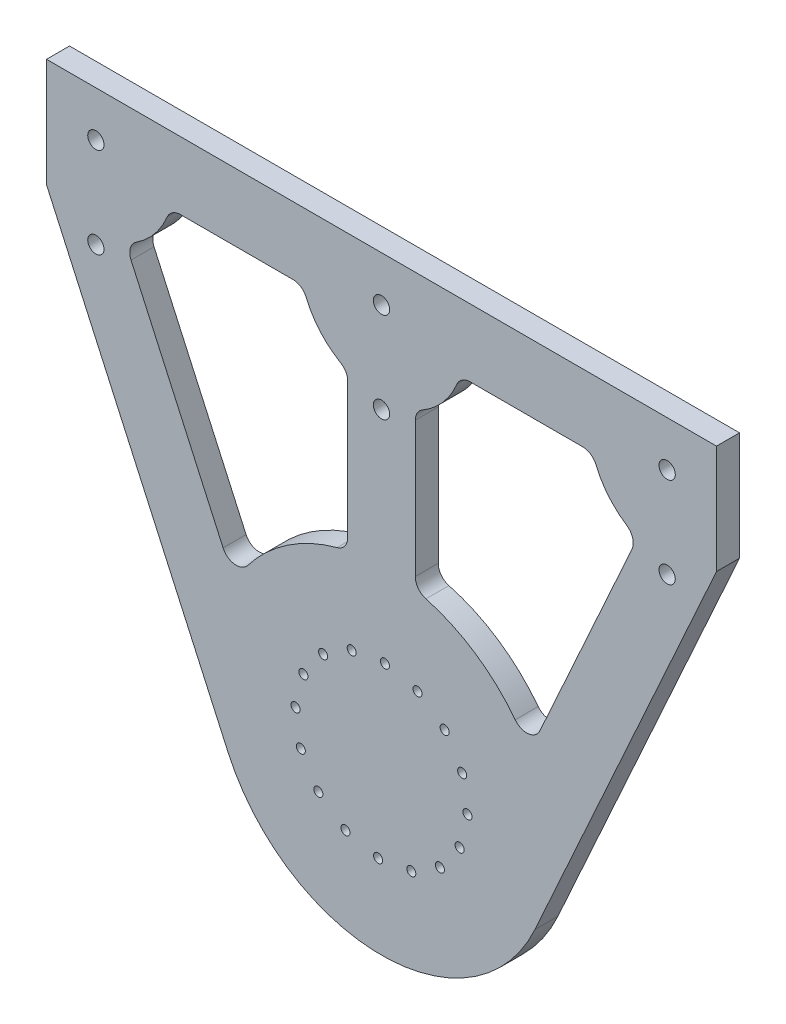
SolidWorks part; units mm, degrees
ref_plane "Front Plane" through (0, 0, 0) normal (0, 0, 1) x (1, 0, 0)
ref_plane "Top Plane" through (0, 0, 0) normal (0, 1, 0) x (1, 0, 0)
ref_plane "Right Plane" through (0, 0, 0) normal (1, 0, 0) x (0, 0, -1)
sketch "Sketch1" plane through (0, 0, 0) normal (0, 0, 1) x (1, 0, 0)
  line L1 (92.5, 121.5) -> (-92.5, 121.5)
  line L3 (0, 0) -> (0, 121.5) construction
  line L4 (-92.5, 121.5) -> (-92.5, 91.5)
  line L5 (-92.5, 91.5) -> (-42.3564, -19.1882)
  line L6 (92.5, 121.5) -> (92.5, 91.5)
  line L7 (92.5, 91.5) -> (42.3564, -19.1882)
  line L8 (42.3564, -19.1882) -> (-42.3564, -19.1882) construction
  circle A0 centre (0, 0) radius 46.5 construction
  arc A1 (-42.3564, -19.1882) -> (42.3564, -19.1882) centre (0, 0) ccw
  dimension "D1" = 93
  dimension "D2" = 185
  dimension "D3" = 121.5
  dimension "D4" = 30
extrude "Boss-Extrude1" add sketch "Sketch1" along normal mid plane 6.35
sketch "Sketch3" plane through (0, 0, -3.175) normal (0, 0, -1) x (-1, 0, 0)
  circle A0 centre (17.4402, -16.1215) radius 1.25 construction
  circle A1 centre (22.282, -8.2203) radius 1.25 construction
  circle A2 centre (9.9432, -21.5684) radius 1.25 construction
  circle A3 centre (0.9324, -23.7317) radius 1.25 construction
  circle A4 centre (-8.2203, -22.282) radius 1.25 construction
  circle A5 centre (-16.1215, -17.4402) radius 1.25 construction
  circle A6 centre (-21.5684, -9.9432) radius 1.25 construction
  circle A7 centre (-23.7317, -0.9324) radius 1.25 construction
  circle A8 centre (-22.282, 8.2203) radius 1.25 construction
  circle A9 centre (-17.4402, 16.1215) radius 1.25 construction
  circle A10 centre (-9.9432, 21.5684) radius 1.25 construction
  circle A11 centre (-0.9324, 23.7317) radius 1.25 construction
  circle A12 centre (8.2203, 22.282) radius 1.25 construction
  circle A13 centre (16.1215, 17.4402) radius 1.25 construction
  circle A14 centre (21.5684, 9.9432) radius 1.25 construction
  circle A15 centre (23.7317, 0.9324) radius 1.25 construction
  circle A16 centre (17.4402, -16.1215) radius 1.25
  circle A17 centre (22.282, -8.2203) radius 1.25
  circle A18 centre (9.9432, -21.5684) radius 1.25
  circle A19 centre (0.9324, -23.7317) radius 1.25
  circle A20 centre (-8.2203, -22.282) radius 1.25
  circle A21 centre (-16.1215, -17.4402) radius 1.25
  circle A22 centre (-21.5684, -9.9432) radius 1.25
  circle A23 centre (-23.7317, -0.9324) radius 1.25
  circle A24 centre (-22.282, 8.2203) radius 1.25
  circle A25 centre (-17.4402, 16.1215) radius 1.25
  circle A26 centre (-9.9432, 21.5684) radius 1.25
  circle A27 centre (-0.9324, 23.7317) radius 1.25
  circle A28 centre (8.2203, 22.282) radius 1.25
  circle A29 centre (16.1215, 17.4402) radius 1.25
  circle A30 centre (21.5684, 9.9432) radius 1.25
  circle A31 centre (23.7317, 0.9324) radius 1.25
extrude "Cut-Extrude2" cut sketch "Sketch3" against normal through all both and the other way through all
ref_plane "Plane1" through (0, 91.5, 0) normal (0, 1, 0) x (1, 0, 0)
ref_plane "Plane2" through (0, 106.5, 0) normal (0, 1, 0) x (1, 0, 0)
sketch "Sketch6" plane through (0, 0, -3.175) normal (0, 0, -1) x (-1, 0, 0)
  line L0 (0, 0) -> (0, 121.5) construction
  line L1 (-92.5, 121.5) -> (-77.5, 121.5) construction
  line L2 (-92.5, 121.5) -> (-92.5, 91.5) construction
  line L3 (-92.5, 91.5) -> (-77.5, 91.5) construction
  line L4 (-77.5, 121.5) -> (-77.5, 91.5) construction
  line L5 (-92.5, 121.5) -> (92.5, 121.5) construction
  line L6 (-85, 121.5) -> (-85, 106.5) construction
  line L11 (-77.5, 106.5) -> (-92.5, 106.5) construction
  line L12 (-7.5, 121.5) -> (7.5, 121.5) construction
  line L13 (-7.5, 121.5) -> (-7.5, 91.5) construction
  line L14 (-7.5, 91.5) -> (7.5, 91.5) construction
  line L15 (7.5, 121.5) -> (7.5, 91.5) construction
  line L16 (-85, 91.5) -> (-85, 106.5) construction
  circle A0 centre (-85, 114) radius 2.25
  circle A1 centre (-85, 99) radius 2.25
  circle A2 centre (0, 114) radius 2.25
  circle A3 centre (0, 99) radius 2.25
  circle A6 centre (85, 114) radius 2.25
  circle A7 centre (85, 99) radius 2.25
  point P18 (0, 121.5)
  point P35 (-85, 114)
  point P38 (-85, 99)
  dimension "D3" = 4.5
  dimension "D1" = 30
  dimension "D2" = 15
sketch "Sketch12" plane through (0, 0, -3.175) normal (0, 0, -1) x (-1, 0, 0)
  line L0 (0, -46.5) -> (0, 121.5) construction
  line L1 (-92.5, 121.5) -> (92.5, 121.5) construction
  line L2 (-87, 116) -> (-92.5, 116) construction
  line L3 (-87, 116) -> (-73, 116) construction
  line L4 (-87, 116) -> (-87, 102) construction
  line L5 (-87, 102) -> (-73, 102) construction
  line L6 (-73, 116) -> (-73, 102) construction
  line L7 (-92.5, 91.5) -> (-92.5, 121.5) construction
  line L8 (-87, 116) -> (-87, 121.5) construction
  line L9 (12.5, 121.5) -> (-12.5, 121.5) construction
  line L11 (-7, 102) -> (7, 102) construction
  line L12 (-7, 102) -> (-7, 116) construction
  line L13 (-7, 116) -> (7, 116) construction
  line L14 (7, 102) -> (7, 116) construction
  circle A0 centre (-7, 102) radius 2.25
  circle A2 centre (7, 102) radius 2.25
  circle A4 centre (7, 116) radius 2.25
  circle A5 centre (-87, 116) radius 2.25
  circle A6 centre (-73, 116) radius 2.25
  circle A7 centre (-73, 102) radius 2.25
  circle A8 centre (-87, 102) radius 2.25
  arc A9 (-42.3564, -19.1882) -> (42.3564, -19.1882) centre (0, 0) ccw construction
  circle A10 centre (87, 102) radius 2.25
  circle A11 centre (73, 102) radius 2.25
  circle A12 centre (73, 116) radius 2.25
  circle A13 centre (87, 116) radius 2.25
  circle A14 centre (-7, 116) radius 2.25
  point P22 (-87, 109)
  point P23 (-7, 109)
  point P24 (0, 116)
  dimension "D3" = 4.5
  dimension "D1" = 5.5
  dimension "D2" = 14
extrude "Cut-Extrude6" cut sketch "Sketch12" against normal through all both and the other way through all
sketch "Sketch13" plane through (0, 0, -3.175) normal (0, 0, -1) x (-1, 0, 0)
  line L0 (-40.7392, 22.418) -> (-70.6842, 88.5191)
  line L1 (40.7392, 22.418) -> (70.6842, 88.5191)
  line L2 (-9.3209, 88.5215) -> (-9.3209, 45.5562)
  line L3 (9.3209, 88.5215) -> (9.3209, 45.5562)
  line L7 (-7, 102) -> (7, 116) construction
  line L8 (-87, 102) -> (-73, 116) construction
  line L9 (58.3545, 102.8582) -> (21.6455, 102.8582)
  line L10 (-58.3545, 102.8582) -> (-21.6455, 102.8582)
  line L11 (25.3758, -11.4957) -> (73.8582, 95.5256)
  line L12 (73.8582, 95.5256) -> (73.8582, 102.8582)
  line L13 (73.8582, 102.8582) -> (-73.8582, 102.8582)
  line L14 (-73.8582, 102.8582) -> (-73.8582, 95.5256)
  line L15 (-73.8582, 95.5256) -> (-25.3758, -11.4957)
  line L16 (25.3758, -11.4957) -> (73.8582, 95.5256) construction
  line L17 (73.8582, 95.5256) -> (73.8582, 102.8582) construction
  line L18 (73.8582, 102.8582) -> (-73.8582, 102.8582) construction
  line L19 (-73.8582, 102.8582) -> (-73.8582, 95.5256) construction
  line L20 (-73.8582, 95.5256) -> (-25.3758, -11.4957) construction
  line L23 (0, 0) -> (0, 109) construction
  arc A0 (-40.7392, 22.418) -> (40.7392, 22.418) centre (0, 0) cw construction
  circle A1 centre (0, 0) radius 27.8582 construction
  arc A2 (-25.3758, -11.4957) -> (25.3758, -11.4957) centre (0, 0) ccw
  arc A3 (-25.3758, -11.4957) -> (25.3758, -11.4957) centre (0, 0) ccw construction
  circle A4 centre (7, 116) radius 2.25 construction
  circle A5 centre (-7, 102) radius 2.25 construction
  circle A6 centre (-73, 116) radius 2.25 construction
  circle A7 centre (-87, 102) radius 2.25 construction
  circle A8 centre (7, 116) radius 2.25 construction
  circle A9 centre (-7, 102) radius 2.25 construction
  circle A10 centre (-73, 116) radius 2.25 construction
  circle A11 centre (-87, 102) radius 2.25 construction
  circle A12 centre (-80, 109) radius 22.5 construction
  circle A13 centre (0, 109) radius 22.5 construction
  circle A14 centre (80, 109) radius 22.5 construction
  arc A15 (-70.6842, 88.5191) -> (-58.3545, 102.8582) centre (-80, 109) ccw
  arc A17 (58.3545, 102.8582) -> (70.6842, 88.5191) centre (80, 109) ccw
  arc A21 (-21.6455, 102.8582) -> (-9.3209, 88.5215) centre (0, 109) ccw
  arc A22 (9.3209, 88.5215) -> (21.6455, 102.8582) centre (0, 109) ccw
  arc A23 (-40.7392, 22.418) -> (-9.3209, 45.5562) centre (0, 0) cw
  arc A24 (9.3209, 45.5562) -> (40.7392, 22.418) centre (0, 0) cw
  dimension "D2" = 45
  dimension "D3" = 18.6418
  dimension "D4" = 46.5
  dimension "D1" = 18.6418
extrude "Cut-Extrude7" cut sketch "Sketch13" against normal through all both and the other way through all
fillet "Fillet4" radius 4 12 edges at (9.3209, 88.5215, 0) (9.3209, 45.5562, 0) (40.7392, 22.418, 0) (-70.6842, 88.5191, 0) (-40.7392, 22.418, 0) (-9.3209, 45.5562, 0) (-9.3209, 88.5215, 0) (-21.6455, 102.8582, 0) (-58.3545, 102.8582, 0) (21.6455, 102.8582, 0) (58.3545, 102.8582, 0) (70.6842, 88.5191, 0)
sketch "Sketch16" plane through (0, 0, 3.175) normal (0, 0, 1) x (1, 0, 0)
  circle A0 centre (-87, 102) radius 2.25 construction
  circle A1 centre (-87, 116) radius 2.25 construction
  circle A2 centre (-73, 116) radius 2.25 construction
  circle A3 centre (-73, 102) radius 2.25 construction
  circle A4 centre (-7, 116) radius 2.25 construction
  circle A5 centre (7, 116) radius 2.25 construction
  circle A6 centre (-7, 102) radius 2.25 construction
  circle A7 centre (7, 102) radius 2.25 construction
  circle A8 centre (73, 102) radius 2.25 construction
  circle A9 centre (87, 102) radius 2.25 construction
  circle A10 centre (73, 116) radius 2.25 construction
  circle A11 centre (87, 116) radius 2.25 construction
  circle A12 centre (-87, 102) radius 2.25
  circle A13 centre (-87, 116) radius 2.25
  circle A14 centre (-73, 116) radius 2.25
  circle A15 centre (-73, 102) radius 2.25
  circle A16 centre (-7, 116) radius 2.25
  circle A17 centre (7, 116) radius 2.25
  circle A18 centre (-7, 102) radius 2.25
  circle A19 centre (7, 102) radius 2.25
  circle A20 centre (73, 102) radius 2.25
  circle A21 centre (87, 102) radius 2.25
  circle A22 centre (73, 116) radius 2.25
  circle A23 centre (87, 116) radius 2.25
extrude "Boss-Extrude2" add sketch "Sketch16" against normal up to surface (6.35 mm away) up to face at (-35.1048, 75.6796, -3.175)
sketch "Sketch17" plane through (0, 0, -3.175) normal (0, 0, -1) x (-1, 0, 0)
  line L0 (0, 84) -> (78.8696, 84) construction
  line L1 (0, 84) -> (0, 121.5) construction
  line L2 (86.1416, 77.4644) -> (69.161, 85.1569) construction
  line L3 (92.5, 91.5) -> (42.3564, -19.1882) construction
  line L4 (69.161, 85.1569) -> (43.7423, 29.047) construction
  line L9 (-92.5, 121.5) -> (92.5, 121.5) construction
  circle A0 centre (78.8696, 84) radius 2.25
  circle A2 centre (0, 84) radius 2.25
  circle A5 centre (-78.8696, 84) radius 2.25
  circle A6 centre (0, 109) radius 2.25
  circle A7 centre (-78.8696, 109) radius 2.25
  circle A8 centre (78.8696, 109) radius 2.25
  dimension "D1" = 4.5
  dimension "D4" = 25
  dimension "D2" = 78.8696
  dimension "D3" = 37.5
extrude "Cut-Extrude8" cut sketch "Sketch17" against normal through all both and the other way through all
